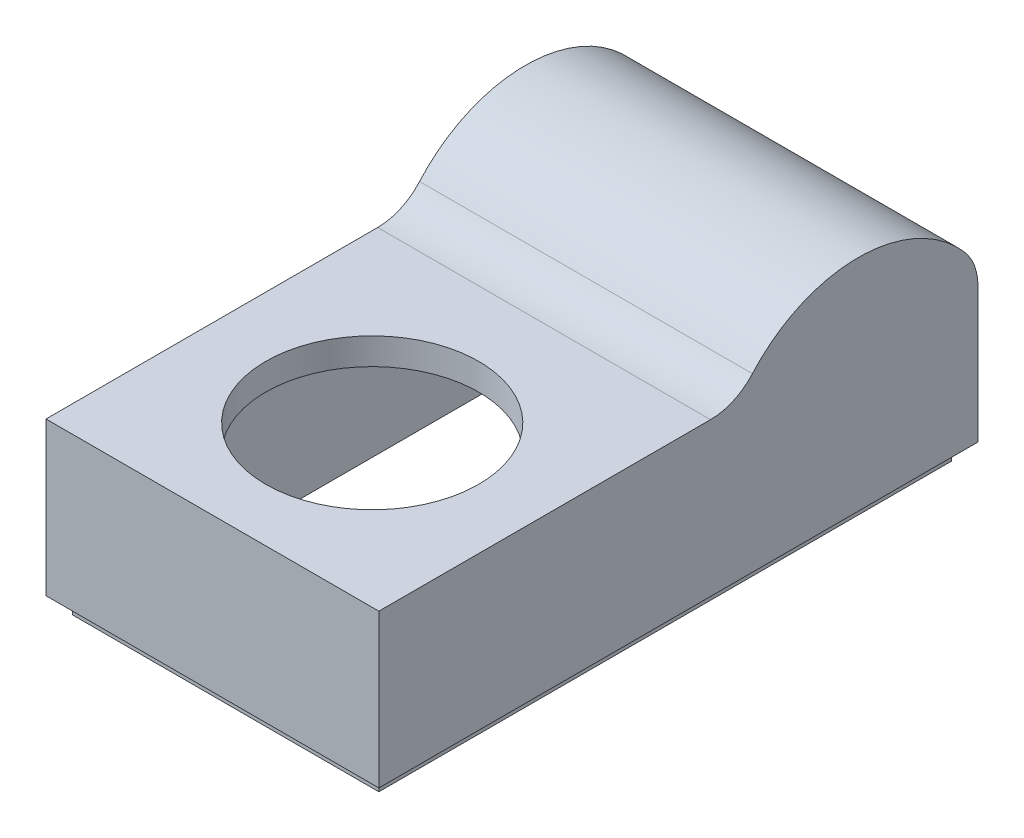
SolidWorks part; units mm, degrees
ref_plane "Front Plane" through (0, 0, 0) normal (0, 0, 1) x (1, 0, 0)
ref_plane "Top Plane" through (0, 0, 0) normal (0, 1, 0) x (1, 0, 0)
ref_plane "Right Plane" through (0, 0, 0) normal (1, 0, 0) x (0, 0, -1)
sketch "Sketch1" plane through (0, 0, 0) normal (0, 1, 0) x (1, 0, 0)
  line L1 (-15.875, 28.575) -> (15.875, 28.575)
  line L2 (-15.875, 28.575) -> (-15.875, -28.575)
  line L3 (-15.875, -28.575) -> (15.875, -28.575)
  line L4 (15.875, 28.575) -> (15.875, -28.575)
  point P4 (0, 28.575)
  point P6 (-15.875, 0)
  dimension "D1" = 57.15
  dimension "D2" = 31.75
extrude "Boss-Extrude1" add sketch "Sketch1" along normal mid plane 20.955
sketch "Sketch2" plane through (15.875, 0, 0) normal (1, 0, 0) x (0, 0, -1)
  line L0 (-28.575, 4.1275) -> (5.715, 4.1275)
  line L1 (-28.575, 10.4775) -> (-28.575, -10.4775) construction
  line L2 (28.575, 10.4775) -> (28.575, -10.4775) construction
  line L8 (28.575, 4.1275) -> (28.575, 10.4775)
  line L9 (28.575, 10.4775) -> (-28.575, 10.4775)
  line L10 (-28.575, 10.4775) -> (-28.575, 4.1275)
  arc A0 (5.715, 4.1275) -> (28.575, 4.1275) centre (17.145, -2.9845) cw
  point P9 (17.145, 10.4775)
  line M3 (28.575, -10.4775) -> (28.575, 10.4775)
  line M4 (28.575, 10.4775) -> (-28.575, 10.4775)
  line M5 (-28.575, 10.4775) -> (-28.575, -10.4775)
  dimension "D1" = 6.35
  dimension "D3" = 22.86
extrude "Cut-Extrude1" cut sketch "Sketch2" against normal up to surface (31.75 mm away) contours L0 A0 L9 M5 | A0 M4 M3 region at (15.875, 7.4259, 9.6592) region at (15.875, 8.6855, -25.8695) up to face at (-15.875, 0, 0)
fillet "Fillet1" radius 5.334 1 edges at (0, 4.1275, -5.715)
fillet "Fillet2" radius 5.334 1 edges at (0, 4.1275, -28.575)
shell "Shell1" thickness 2.54 removed face at (0, -10.4775, 0)
sketch "Sketch3" plane through (0, 4.1275, 0) normal (0, 1, 0) x (1, 0, 0)
  line L0 (-15.875, -13.335) -> (15.875, -13.335) construction
  line L1 (-15.875, 3.06) -> (-15.875, -28.575) construction
  line L2 (15.875, -28.575) -> (15.875, 3.06) construction
  line L4 (0, -3.175) -> (0, -23.495) construction
  line L5 (-15.875, -28.575) -> (15.875, -28.575) construction
  circle A0 centre (0, -13.335) radius 10.16
  point P9 (0, -13.335)
  dimension "D2" = 20.32
  dimension "D1" = 5.08
extrude "Cut-Extrude2" cut sketch "Sketch3" against normal blind 24.13
sketch "Sketch5" plane through (0, 0, -28.575) normal (0, 0, -1) x (-1, 0, 0)
  line L0 (-15.875, -10.4775) -> (15.875, -10.4775) construction
  line L1 (-5.3975, -10.4775) -> (5.3975, -10.4775)
  line L2 (-5.3975, -10.4775) -> (-5.3975, -8.4455)
  line L3 (-5.3975, -8.4455) -> (5.3975, -8.4455)
  line L4 (5.3975, -10.4775) -> (5.3975, -8.4455)
  point P6 (0, -8.4455)
  dimension "D1" = 2.032
  dimension "D2" = 10.795
extrude "Cut-Extrude3" cut sketch "Sketch5" against normal up to surface (2.54 mm away) up to face at (0, -4.0429, -26.035)
sketch "Sketch4" plane through (0, -10.4775, 0) normal (0, -1, 0) x (1, 0, 0)
  line L0 (-5.3975, -26.035) -> (-13.335, -26.035) construction
  line L1 (13.335, -26.035) -> (5.3975, -26.035) construction
  line L2 (13.335, 26.035) -> (13.335, -26.035) construction
  line L3 (-13.335, 26.035) -> (13.335, 26.035) construction
  line L4 (-13.335, -26.035) -> (-13.335, 26.035) construction
  line L5 (-5.3975, -26.035) -> (-13.335, -26.035)
  line L6 (13.335, -26.035) -> (5.3975, -26.035)
  line L7 (13.335, 26.035) -> (13.335, -26.035)
  line L8 (-13.335, 26.035) -> (13.335, 26.035)
  line L9 (-13.335, -26.035) -> (-13.335, 26.035)
  line L10 (-5.3975, -27.305) -> (-5.3975, -26.035)
  line L11 (5.3975, -27.305) -> (5.3975, -26.035)
  line L56 (-14.605, 27.305) -> (-14.605, -27.305)
  line L57 (-14.605, -27.305) -> (-5.3975, -27.305)
  line L58 (-5.3975, -27.305) -> (5.3975, -27.305)
  line L59 (5.3975, -27.305) -> (14.605, -27.305)
  line L60 (14.605, -27.305) -> (14.605, 27.305)
  line L61 (14.605, 27.305) -> (-14.605, 27.305)
  line L62 (-14.605, 27.305) -> (-14.605, -27.305)
  line L63 (-14.605, -27.305) -> (-5.3975, -27.305)
  line L65 (5.3975, -27.305) -> (14.605, -27.305)
  line L66 (14.605, -27.305) -> (14.605, 27.305)
  line L67 (14.605, 27.305) -> (-14.605, 27.305)
  dimension "D1" = 1.27
extrude "Boss-Extrude2" add sketch "Sketch4" along normal blind 1.5875
